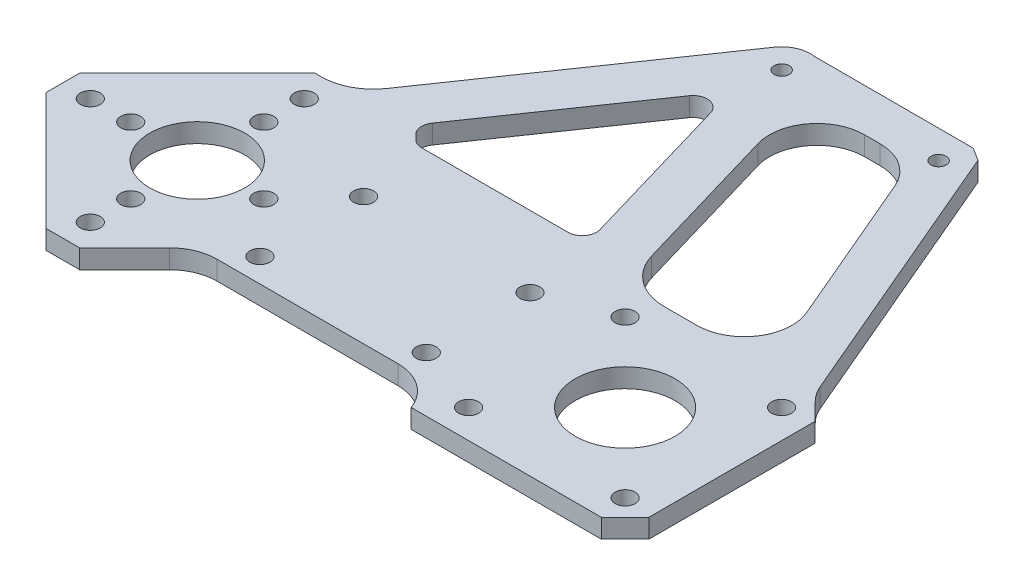
SolidWorks part; units mm, degrees
ref_plane "前视基准面" through (0, 0, 0) normal (0, 0, 1) x (1, 0, 0)
ref_plane "上视基准面" through (0, 0, 0) normal (0, 1, 0) x (1, 0, 0)
ref_plane "右视基准面" through (0, 0, 0) normal (1, 0, 0) x (0, 0, -1)
sketch "草图1" plane through (0, 0, 0) normal (0, 1, 0) x (1, 0, 0)
  line L0 (0, 0) -> (-31.8198, 0) construction
  line L1 (0, 31.8198) -> (-31.8198, 0)
  line L2 (-31.8198, 0) -> (0, -31.8198)
  line L3 (0, -31.8198) -> (15.9099, -15.9099)
  line L4 (15.9099, 15.9099) -> (0, 31.8198)
  line L5 (0, 0) -> (90, 0) construction
  line L6 (0, 0) -> (45, 77.9423) construction
  line L7 (45, 77.9423) -> (90, 0) construction
  line L8 (15.9099, 15.9099) -> (67.5, 15.9099)
  line L9 (15.9099, -15.9099) -> (67.5, -15.9099)
  line L10 (90, 0) -> (67.5, -22.5) construction
  line L11 (67.5, 22.5) -> (67.5, 15.9099)
  line L12 (67.5, -22.5) -> (112.5, -22.5)
  line L13 (112.5, -22.5) -> (112.5, 22.5)
  line L14 (112.5, 22.5) -> (67.5, 22.5)
  line L15 (67.5, -15.9099) -> (67.5, -22.5)
  line L16 (0, 0) -> (15.9099, 15.9099) construction
  line L17 (0, 0) -> (15.9099, -15.9099) construction
  circle A0 centre (0, 14) radius 2.1
  circle A1 centre (14, 0) radius 2.1
  circle A2 centre (0, -14) radius 2.1
  circle A3 centre (-14, 0) radius 2.1
  circle A4 centre (0, 0) radius 22.5 construction
  arc A5 (45, -77.9423) -> (45, 77.9423) centre (0, 0) ccw construction
  arc A6 (45, 77.9423) -> (45, -77.9423) centre (90, 0) ccw construction
  circle A7 centre (90, 0) radius 10.5
  circle A8 centre (90, 0) radius 22.5 construction
  circle A9 centre (0, 22.5) radius 2.1
  circle A11 centre (0, -22.5) radius 2.1
  circle A12 centre (0, 0) radius 10
  circle A13 centre (0, 0) radius 14 construction
  circle A14 centre (-22.5, 0) radius 2.1
  dimension "D1" = 4.2
  dimension "D2" = 20
  dimension "D3" = 4.2
  dimension "D4" = 4.2
  dimension "D5" = 4.2
  dimension "D6" = 45
  dimension "D9" = 180
  dimension "D10" = 180
  dimension "D11" = 21
  dimension "D14" = 4.2
  dimension "D15" = 4.2
  dimension "D17" = 4.2
  dimension "D7" = 180
  dimension "D8" = 90
  dimension "D12" = 135
  dimension "D13" = 45
extrude "凸台-拉伸1" add sketch "草图1" along normal blind 4
chamfer "倒角1" distance 5 angle 45 5 edges at (112.5, 2, 22.5) (112.5, 2, -22.5) (0, 2, 31.8198) (-31.8198, 2, 0) (0, 2, -31.8198)
fillet "圆角1" radius 10 4 edges at (15.9099, 2, -15.9099) (15.9099, 2, 15.9099) (67.5, 2, 15.9099) (67.5, 2, -15.9099)
sketch "草图2" plane through (0, 0, 0) normal (0, -1, 0) x (1, 0, 0)
  line L0 (39.0757, 15.9099) -> (39.0757, 10.9099) construction
  line L1 (20.052, 15.9099) -> (58.0993, 15.9099) construction
  line L2 (39.0757, 10.9099) -> (24.0757, 10.9099) construction
  line L3 (39.0757, 10.9099) -> (59.0757, 10.9099) construction
  line L4 (110, 20) -> (90, 0) construction
  line L5 (112.5, 17.5) -> (107.5, 22.5) construction
  line L6 (110, -20) -> (90, 0) construction
  line L7 (107.5, -22.5) -> (112.5, -17.5) construction
  line L8 (90, 22.5) -> (90, -22.5) construction
  line L9 (67.5, 22.5) -> (107.5, 22.5) construction
  line L10 (107.5, -22.5) -> (67.5, -22.5) construction
  line L11 (70, -20) -> (90, 0) construction
  line L12 (70, 20) -> (90, 0) construction
  line L13 (0, 0) -> (90, 0) construction
  line L14 (39.0757, -10.9099) -> (59.0757, -10.9099) construction
  line L15 (39.0757, -10.9099) -> (24.0757, -10.9099) construction
  line L16 (39.0757, -15.9099) -> (39.0757, -10.9099) construction
  circle A0 centre (106.4645, 16.4645) radius 2.1
  circle A1 centre (106.4645, -16.4645) radius 2.1
  circle A2 centre (73.5355, -16.4645) radius 2.1
  circle A3 centre (73.5355, 16.4645) radius 2.1
  circle A4 centre (24.0757, 10.9099) radius 2.1
  circle A5 centre (59.0757, 10.9099) radius 2.1
  circle A6 centre (59.0757, -10.9099) radius 2.1
  circle A7 centre (24.0757, -10.9099) radius 2.1
  dimension "D3" = 4.2
  dimension "D4" = 4.2
  dimension "D5" = 20
  dimension "D6" = 15
  dimension "D8" = 4.2
  dimension "D9" = 4.2
  dimension "D1" = 5
  dimension "D2" = 5
  dimension "D7" = 5
extrude "切除-拉伸1" cut sketch "草图2" against normal blind 10
sketch "草图3" plane through (0, 4, 0) normal (0, 1, 0) x (1, 0, 0)
  line L0 (0, 0) -> (90, 0) construction
  line L1 (45, 0) -> (45, 77.9423) construction
  line L2 (3.5355, 28.2843) -> (40.0576, 81.3442)
  line L3 (67.5, 22.5) -> (50.7578, 79.6297)
  line L4 (12.981, 18.8388) -> (3.5355, 28.2843) construction
  line L5 (58.0993, 15.9099) -> (20.052, 15.9099) construction
  line L6 (12.981, 18.8388) -> (3.5355, 28.2843)
  line L7 (58.0993, 15.9099) -> (20.052, 15.9099)
  line L8 (16.4918, 29.4702) -> (43.5266, 68.7468)
  line L9 (56.0801, 25.9099) -> (43.5266, 68.7468)
  line L10 (56.0801, 25.9099) -> (20.052, 25.9099)
  line L11 (20.052, 25.9099) -> (16.4918, 29.4702)
  circle A0 centre (45, 77.9423) radius 1.6
  arc A1 (50.7578, 79.6297) -> (40.0576, 81.3442) centre (45, 77.9423) ccw
  arc A2 (12.981, 18.8388) -> (20.052, 15.9099) centre (20.052, 25.9099) ccw construction
  arc A3 (58.0993, 15.9099) -> (67.5, 22.5) centre (58.0993, 25.9099) ccw construction
  arc A4 (12.981, 18.8388) -> (20.052, 15.9099) centre (20.052, 25.9099) ccw
  arc A5 (58.0993, 15.9099) -> (67.5, 22.5) centre (58.0993, 25.9099) ccw
  arc A6 (43.5266, 68.7468) -> (43.5266, 68.7468) centre (43.5266, 68.7468) ccw
  arc A7 (56.0801, 25.9099) -> (56.0801, 25.9099) centre (56.0801, 25.9099) ccw
  arc A8 (20.052, 25.9099) -> (20.052, 25.9099) centre (20.052, 25.9099) ccw
  dimension "D1" = 3.2
  dimension "D2" = 12
  dimension "D3" = 10
extrude "凸台-拉伸2" add sketch "草图3" against normal blind 4
fillet "圆角2" radius 3 4 edges at (20.052, 2, -25.9099) (16.4918, 2, -29.4702) (56.0801, 2, -25.9099) (43.5266, 2, -68.7468)
fillet "圆角3" radius 11 2 edges at (3.5355, 2, -28.2843) (67.5, 2, -22.5)
sketch "草图4" plane through (0, 4, 0) normal (0, 1, 0) x (1, 0, 0)
  line L0 (45.9493, 83.8667) -> (81.3477, 83.8667)
  line L3 (81.3477, 83.8667) -> (107.5, 22.5)
  line L4 (52.1537, 74.8667) -> (75.4, 74.8667)
  line L5 (75.4, 74.8667) -> (97.7168, 22.5)
  line L6 (107.5, 22.5) -> (75.739, 22.5) construction
  line L7 (73.0682, 80.3383) -> (99.2205, 18.9716) construction
  line L8 (45.9493, 74.8667) -> (90, 74.8667) construction
  line L9 (107.5, 22.5) -> (97.7168, 22.5)
  line L10 (65.183, 30.4065) -> (50.7578, 79.6297) construction
  line L11 (52.1537, 74.8667) -> (50.7578, 79.6297)
  line L12 (45.9493, 83.8667) -> (90, 83.8667) construction
  arc A0 (50.7578, 79.6297) -> (40.0576, 81.3442) centre (45, 77.9423) ccw construction
  circle A2 centre (78, 77.9423) radius 1.6
  arc A3 (50.7578, 79.6297) -> (45.9493, 83.8667) centre (45, 77.9423) ccw
  dimension "D1" = 33
extrude "凸台-拉伸3" add sketch "草图4" against normal blind 4
fillet "圆角4" radius 10 3 edges at (75.4, 2, -74.8667) (97.7168, 2, -22.5) (52.1537, 2, -74.8667)
chamfer "倒角2" distance 2 angle 32 1 edges at (81.3477, 2, -83.8667) first distance on face at (63.6485, 2, -83.8667)
fillet "圆角5" radius 10 1 edges at (107.5, 2, -22.5)
